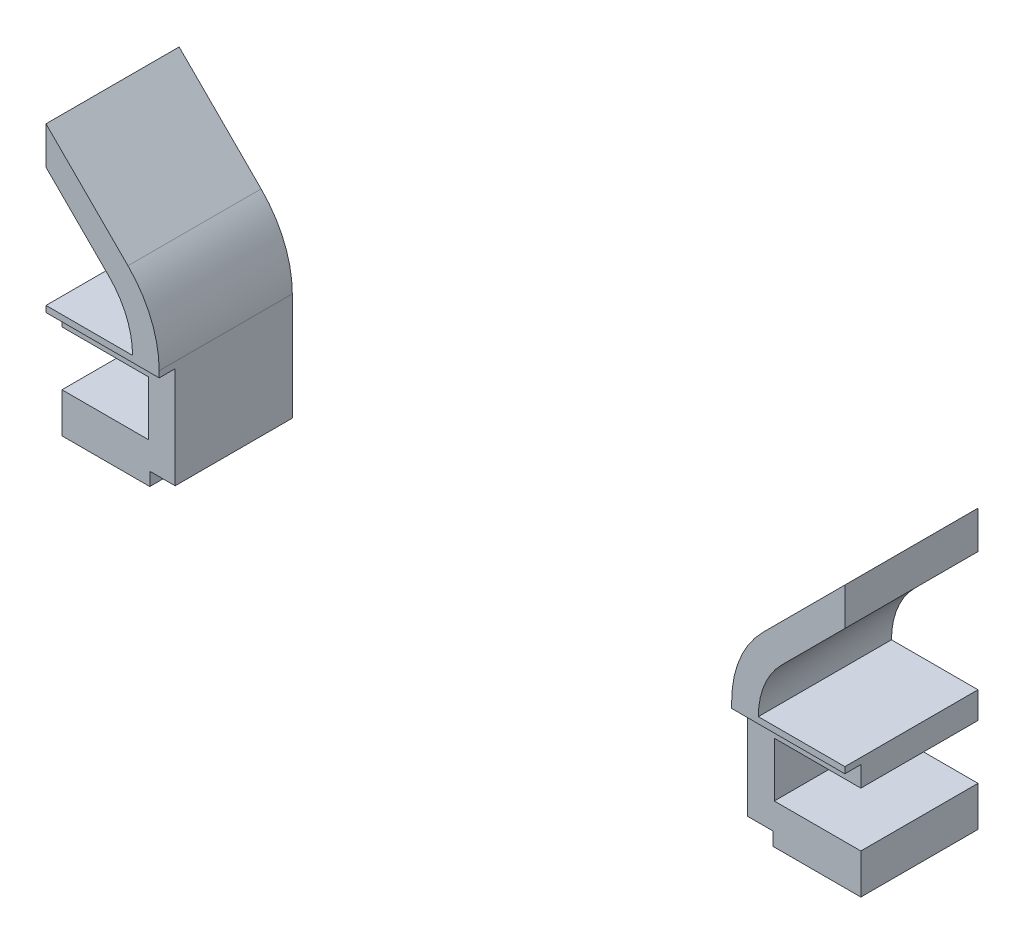
SolidWorks part; units mm, degrees
ref_plane "Front Plane" through (0, 0, 0) normal (0, 0, 1) x (1, 0, 0)
ref_plane "Top Plane" through (0, 0, 0) normal (0, 1, 0) x (1, 0, 0)
ref_plane "Right Plane" through (0, 0, 0) normal (1, 0, 0) x (0, 0, -1)
sketch "Sketch1" plane through (0, 0, 0) normal (0, 0, 1) x (1, 0, 0)
  line L0 (300, 74) -> (238.4315, 12.4315) construction
  line L2 (300, 74) -> (238.4315, 12.4315)
  line L4 (234.05, -125) -> (215, -125) construction
  line L5 (234.05, -125) -> (215, -125)
  line L6 (234.05, -125) -> (300, -125)
  line L7 (300, 300) -> (300, -135) construction
  line L8 (300, -125) -> (300, -105)
  line L9 (215, -125) -> (215, -105)
  line L10 (215, -105) -> (215, -44.1371)
  line L11 (300, 74) -> (300, 45.7157)
  line L12 (235, -105) -> (235, -64.1371)
  line L13 (300, 45.7157) -> (252.5736, -1.7107)
  line L14 (235, -105) -> (300, -105)
  line L15 (235, -44.1371) -> (300, -44.1371)
  line L16 (235, -125) -> (235, -105) construction
  line L17 (314.1421, 59.8579) -> (252.5736, -1.7107) construction
  line L18 (300, -44.1371) -> (300, -64.1371)
  line L19 (300, -64.1371) -> (235, -64.1371)
  line L21 (235, -105) -> (235, -44.1371) construction
  arc A0 (238.4315, 12.4315) -> (215, -44.1371) centre (295, -44.1371) ccw construction
  arc A1 (238.4315, 12.4315) -> (215, -44.1371) centre (295, -44.1371) ccw
  arc A2 (252.5736, -1.7107) -> (235, -44.1371) centre (295, -44.1371) ccw
  dimension "D1" = 20
extrude "Boss-Extrude1" add sketch "Sketch1" along normal up to surface (100 mm away)
sketch "Sketch2" plane through (215, 0, 0) normal (-1, 0, 0) x (0, 0, 1)
  line L0 (88, -125) -> (100, -125) construction
  line L1 (88, -48.8) -> (88, -125) construction
  line L2 (100, -48.8) -> (88, -48.8) construction
  line L3 (88, -125) -> (100, -125)
  line L4 (88, -48.8) -> (88, -125)
  line L5 (100, -48.8) -> (88, -48.8)
  line L6 (100, -48.8) -> (100, -125)
extrude "Cut-Extrude1" cut sketch "Sketch2" against normal through all
sketch "Sketch3" plane through (0, -125, 0) normal (0, -1, 0) x (1, 0, 0)
  line L1 (215, 0) -> (300, 0) construction
  line L2 (234.05, 0) -> (234.05, 88)
  line L3 (300, 88) -> (215, 88) construction
  line L4 (234.05, 88) -> (300, 88)
  line L5 (300, 88) -> (300, 0)
  line L6 (300, 0) -> (234.05, 0)
extrude "Boss-Extrude2" add sketch "Sketch3" along normal blind 10
mirror "Mirror1" about plane through (0, 0, 0) normal (1, 0, 0) of bodies 103
